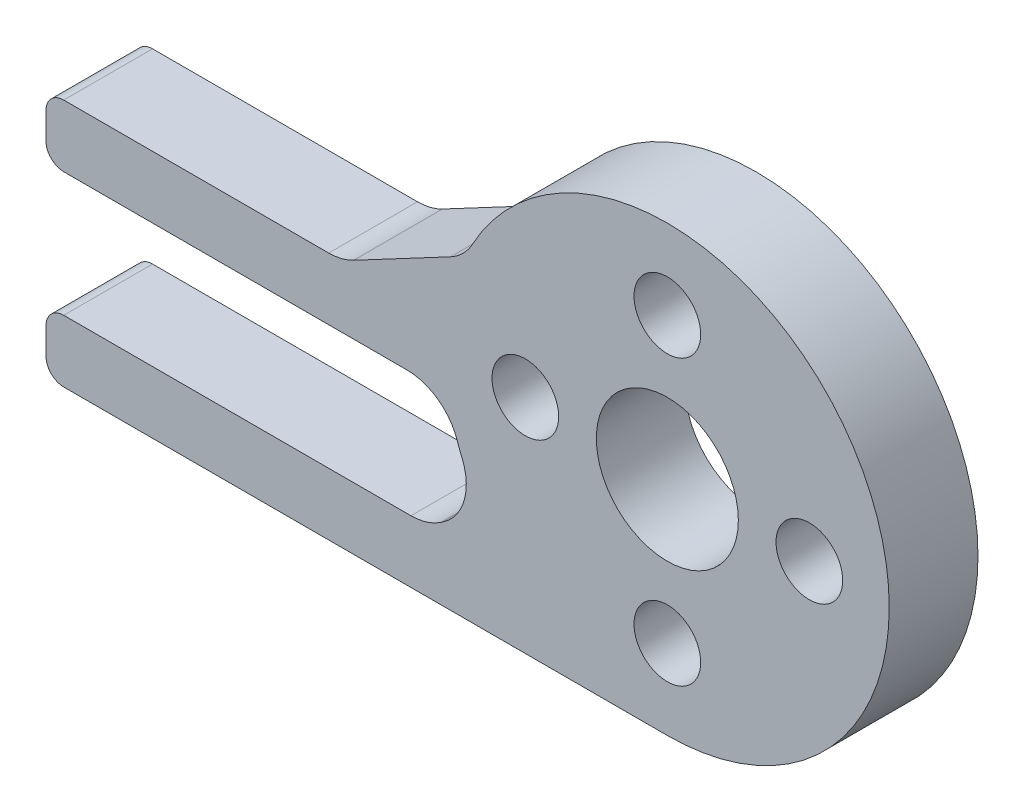
SolidWorks part; units mm, degrees
ref_plane "Front Plane" through (0, 0, 0) normal (0, 0, 1) x (1, 0, 0)
ref_plane "Top Plane" through (0, 0, 0) normal (0, 1, 0) x (1, 0, 0)
ref_plane "Right Plane" through (0, 0, 0) normal (1, 0, 0) x (0, 0, -1)
sketch "Sketch1" plane through (0, 0, 0) normal (0, 0, 1) x (1, 0, 0)
  line L0 (0, -12.5) -> (-35, -12.5)
  line L1 (-10.4226, -6.9007) -> (-13.5218, -9)
  line L2 (-35, -2) -> (-12.339, -2)
  line L3 (-35, -2) -> (-12.339, -2)
  line L4 (-35, -2) -> (-35, 1.5)
  line L5 (-35, 1.5) -> (-12.4097, 1.5)
  line L7 (-35, -12.5) -> (0, -12.5)
  line L8 (-35, -12.5) -> (-35, -9)
  line L9 (-35, -9) -> (-13.5218, -9)
  circle A1 centre (0, 8) radius 1.878
  circle A2 centre (8, 0) radius 1.878
  circle A3 centre (0, -8) radius 1.878
  circle A4 centre (-8, 0) radius 1.878
  circle A5 centre (0, 0) radius 4
  arc A6 (0, -12.5) -> (-12.4097, 1.5) centre (0, 0) ccw
  arc A7 (-12.339, -2) -> (-10.4226, -6.9007) centre (0, 0) ccw
  point P14 (0, 0)
  dimension "D1" = 25
  dimension "D2" = 3.756
  dimension "D4" = 8
  dimension "D5" = 35
  dimension "D6" = 10.5
  dimension "D7" = 3.5
  dimension "D8" = 3.5
  dimension "D3" = 4
extrude "Boss-Extrude1" add sketch "Sketch1" along normal blind 5 contours L2 A7 L9 L8 L0 A6 L5 L4 A1 A2 A3 A4 A5 region at (-6.8767, -1.9943, 0)
chamfer "Chamfer1" distance 6 angle 45 1 edges at (-12.4097, 1.5, 2.5) first distance on face at (1.5747, 1.3958, 2.5)
fillet "Fillet1" radius 3 3 edges at (-12.339, -2, 2.5) (-10.4226, -6.9007, 2.5) (-13.5218, -9, 2.5)
fillet "Fillet2" radius 3 2 edges at (-11.3693, 5.1952, 2.5) (-18.3272, 1.5, 2.5)
fillet "Fillet3" radius 1 2 edges at (-35, -2, 2.5) (-35, -9, 2.5)
fillet "Fillet4" radius 1 2 edges at (-35, -12.5, 2.5) (-35, 1.5, 2.5)
